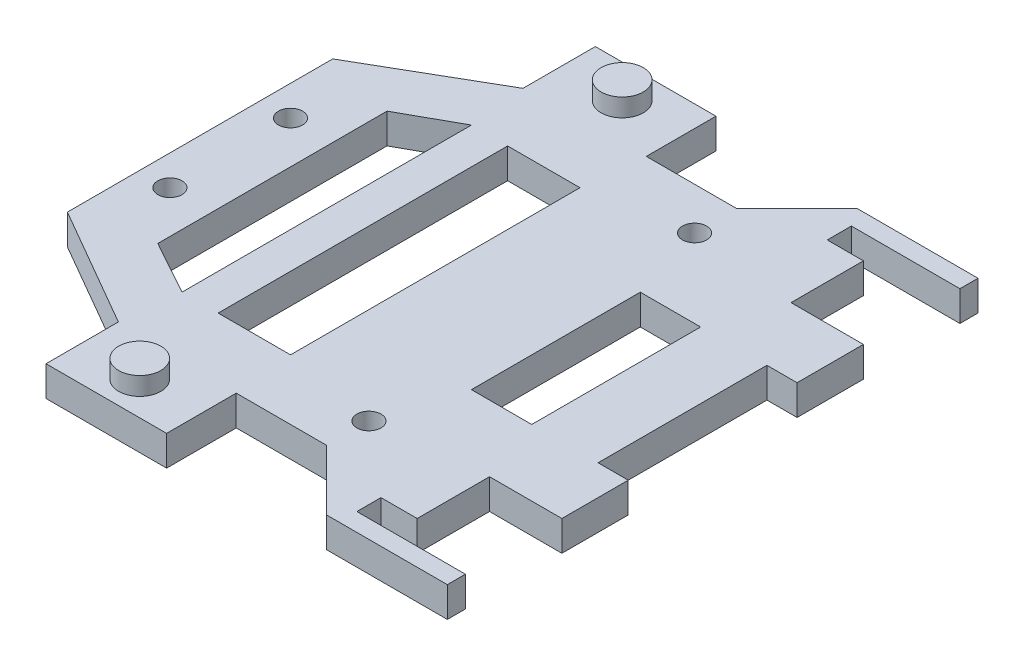
SolidWorks part; units mm, degrees
material "Plain Carbon Steel"
ref_plane "Front Plane" through (0, 0, 0) normal (0, 0, 1) x (1, 0, 0)
ref_plane "Top Plane" through (0, 0, 0) normal (0, 1, 0) x (1, 0, 0)
ref_plane "Right Plane" through (0, 0, 0) normal (1, 0, 0) x (0, 0, -1)
sketch "Sketch3" plane through (0, 0, 0) normal (0, 1, 0) x (1, 0, 0)
  line L0 (0, 0) -> (138, 0) construction
  line L1 (0, -22) -> (0, 22)
  line L2 (0, 22) -> (20, 33.547)
  line L3 (20, 33.547) -> (20, 45.547)
  line L4 (20, 45.547) -> (40, 45.547)
  line L5 (40, 45.547) -> (40, 34)
  line L6 (40, 34) -> (55, 34)
  line L7 (55, 34) -> (65, 44)
  line L8 (65, 44) -> (85, 44)
  line L9 (85, 44) -> (85, 41)
  line L10 (85, 41) -> (67, 41)
  line L11 (67, 41) -> (67, 37)
  line L12 (67, 37) -> (73, 37)
  line L13 (73, 37) -> (73, 25)
  line L14 (73, 25) -> (85, 25)
  line L15 (85, 25) -> (85, 14)
  line L16 (85, 14) -> (80, 14)
  line L17 (80, 14) -> (80, -14)
  line L18 (27, 24) -> (27, -24)
  line L19 (27, 24) -> (39, 24)
  line L20 (39, 24) -> (39, -24)
  line L21 (59, 14) -> (69, 14)
  line L22 (69, 14) -> (69, -14)
  line L23 (59, 14) -> (59, -14)
  line L24 (59, -14) -> (69, -14)
  line L25 (27, -24) -> (39, -24)
  line L26 (85, -14) -> (80, -14)
  line L27 (85, -25) -> (85, -14)
  line L28 (73, -25) -> (85, -25)
  line L29 (73, -37) -> (73, -25)
  line L30 (67, -37) -> (73, -37)
  line L31 (67, -41) -> (67, -37)
  line L32 (85, -41) -> (67, -41)
  line L33 (85, -44) -> (85, -41)
  line L34 (65, -44) -> (85, -44)
  line L35 (55, -34) -> (65, -44)
  line L36 (40, -34) -> (55, -34)
  line L37 (40, -45.547) -> (40, -34)
  line L38 (20, -45.547) -> (40, -45.547)
  line L39 (20, -33.547) -> (20, -45.547)
  line L40 (0, -22) -> (20, -33.547)
  line L41 (12, 19) -> (12, -19)
  line L42 (12, 19) -> (21, 24)
  line L43 (21, 24) -> (21, -24)
  line L44 (12, -19) -> (21, -24)
  circle A0 centre (55, 27) radius 2
  circle A1 centre (30, 40) radius 3.5
  circle A2 centre (5, 10) radius 2
  circle A3 centre (5, -10) radius 2
  circle A4 centre (30, -40) radius 3.5
  circle A5 centre (55, -27) radius 2
  point P41 (59, 0)
  point P42 (69, 0)
  point P43 (39, 0)
  point P44 (27, 0)
  point P45 (80, 0)
  point P62 (0, 0)
  point P66 (12, 0)
  point P67 (21, 0)
  dimension "D22" = 4
  dimension "D23" = 7
  dimension "D24" = 4
  dimension "D1" = 44
  dimension "D2" = 30
  dimension "D3" = 20
  dimension "D4" = 20
  dimension "D5" = 12
  dimension "D6" = 15
  dimension "D7" = 10
  dimension "D8" = 45
  dimension "D9" = 30
  dimension "D10" = 3
  dimension "D11" = 4
  dimension "D12" = 12
  dimension "D13" = 68
  dimension "D14" = 28
  dimension "D15" = 11
  dimension "D16" = 48
  dimension "D17" = 12
  dimension "D18" = 41
  dimension "D19" = 10
  dimension "D20" = 11
  dimension "D21" = 5
  dimension "D25" = 55
  dimension "D26" = 40
  dimension "D27" = 20
  dimension "D28" = 80
  dimension "D29" = 54
  dimension "D30" = 18
  dimension "D31" = 38
  dimension "D32" = 9
  dimension "D33" = 59
extrude "Boss-Extrude1" add sketch "Sketch3" along normal blind 5
extrude "Boss-Extrude2" add sketch "Sketch3<2>" along normal blind 8 contours A1 | A4 region at (30, 0, -40)
sketch "Sketch3<2>" plane through (0, 0, 0) normal (0, 1, 0) x (1, 0, 0) same geometry as "Sketch3"
